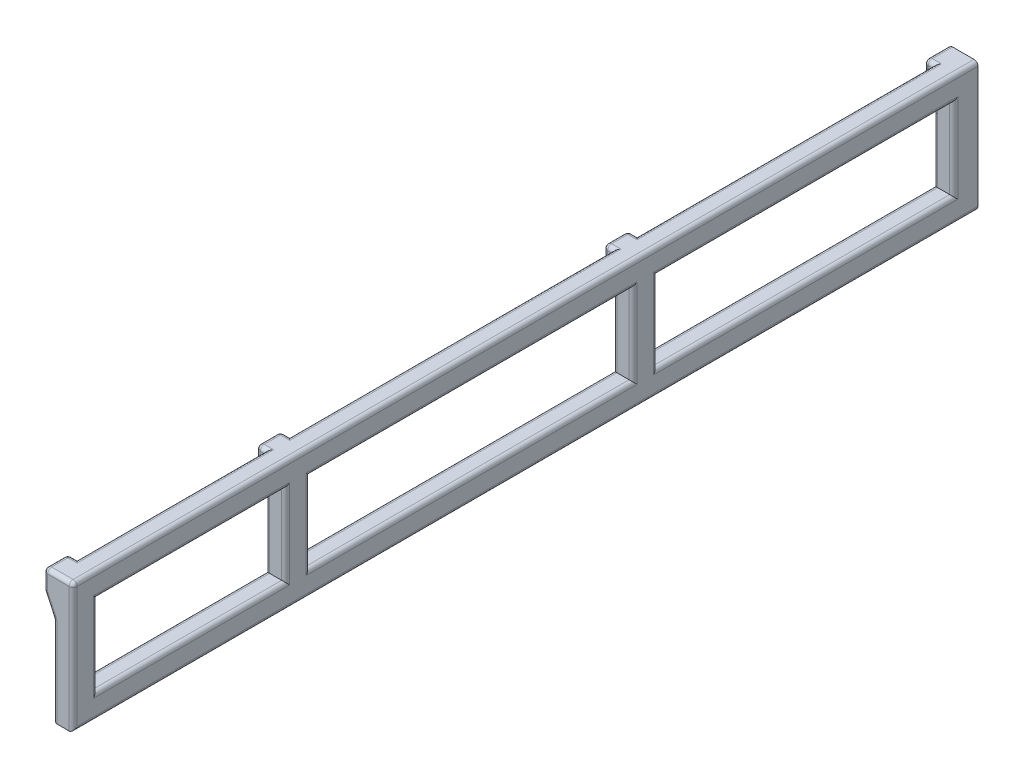
SolidWorks part; units mm, degrees
ref_plane "Plano frontal" through (0, 0, 0) normal (0, 0, 1) x (1, 0, 0)
ref_plane "Plano superior" through (0, 0, 0) normal (0, 1, 0) x (1, 0, 0)
ref_plane "Plano direito" through (0, 0, 0) normal (1, 0, 0) x (0, 0, -1)
sketch "Esboço8" plane through (0, 0, 0) normal (1, 0, 0) x (0, 0, -1)
  line L0 (-69.8214, 36) -> (10.1786, 36)
  line L1 (95.5586, 10) -> (-128.4414, 10)
  line L3 (89.5586, 16) -> (16.1786, 16)
  line L5 (-128.4414, 42) -> (70.1715, 42)
  line L7 (-122.4414, 36) -> (-75.8214, 36)
  line L8 (89.5586, 36) -> (89.5586, 16)
  line L10 (-75.8214, 36) -> (-75.8214, 16)
  line L12 (-69.8214, 36) -> (-69.8214, 16)
  line L14 (16.1786, 36) -> (16.1786, 16)
  line L16 (10.1786, 36) -> (10.1786, 16)
  line L17 (-75.8214, 16) -> (-122.4414, 16)
  line L18 (16.1786, 36) -> (89.5586, 36)
  line L19 (10.1786, 16) -> (-69.8214, 16)
  line L20 (-128.4414, 42) -> (-128.4414, 10)
  line L22 (-122.4414, 16) -> (-122.4414, 36)
  line L24 (70.1715, 42) -> (95.5586, 42)
  line L25 (95.5586, 42) -> (95.5586, 10)
  dimension "D2" = 224
  dimension "D3" = 80
  dimension "D4" = 52.62
  dimension "D5" = 6
  dimension "D6" = 20
  dimension "D8" = 6
  dimension "D9" = 6
  dimension "D10" = 6
extrude "Ressalto-extrusão1" add sketch "Esboço8" against normal blind 5
sketch "Esboço9" plane through (0, 0, 75.8214) normal (0, 0, 1) x (1, 0, 0)
  line L1 (-7.2996, 42) -> (-5, 42)
  line L4 (-5, 42) -> (-5, 32.1044)
  line L6 (-7.2996, 37.0359) -> (-5, 32.1044)
  line L7 (-7.2996, 42) -> (-7.2996, 37.0359)
extrude "Ressalto-extrusão2" add sketch "Esboço9" against normal blind 6
sketch "Esboço10" plane through (0, 0, -10.1786) normal (0, 0, 1) x (1, 0, 0)
  line L8 (0, 16) -> (0, 36)
  line L9 (0, 36) -> (-5, 36)
  line L10 (-5, 36) -> (-5, 42)
  line L11 (-5, 42) -> (-7.2996, 42)
  line L12 (-5, 42) -> (-7.2996, 42)
  line L13 (-7.2996, 42) -> (-7.2996, 37.0359)
  line L14 (-7.2996, 42) -> (-7.2996, 37.0359)
  line L15 (-5, 16) -> (0, 16)
  line L18 (-5, 32.1044) -> (-5, 42)
  line L22 (-7.2996, 37.0359) -> (-5, 32.1044)
  line L23 (-7.2996, 37.0359) -> (-5, 32.1044)
  line L24 (-5, 32.1044) -> (-5, 16)
  line M11 (-5, 36) -> (-5, 16)
  dimension "D1" = 0
extrude "Ressalto-extrusão3" add sketch "Esboço10" against normal blind 6 contours L14 L23 L18 L12 M11 region at (-6.0226, 38.1487, -10.1786)
sketch "Esboço11" plane through (0, 0, 128.4414) normal (0, 0, 1) x (1, 0, 0)
  line L8 (0, 16) -> (0, 36)
  line L9 (0, 36) -> (-5, 36)
  line L10 (-5, 36) -> (-5, 42)
  line L11 (-5, 42) -> (-7.2996, 42)
  line L12 (-5, 42) -> (-7.2996, 42)
  line L13 (-7.2996, 42) -> (-7.2996, 37.0359)
  line L14 (-7.2996, 42) -> (-7.2996, 37.0359)
  line L15 (-5, 16) -> (0, 16)
  line L18 (-5, 32.1044) -> (-5, 42)
  line L22 (-7.2996, 37.0359) -> (-5, 32.1044)
  line L23 (-7.2996, 37.0359) -> (-5, 32.1044)
  line L24 (-5, 32.1044) -> (-5, 16)
  line M11 (-5, 42) -> (-5, 10)
  dimension "D1" = 0
extrude "Ressalto-extrusão4" add sketch "Esboço11" against normal blind 6 contours L14 L23 L12 M11 region at (-6.0226, 38.1487, 128.4414)
sketch "Esboço12" plane through (0, 0, -89.5586) normal (0, 0, 1) x (1, 0, 0)
  line L6 (0, 10) -> (0, 42)
  line L7 (0, 42) -> (-7.2996, 42)
  line L8 (-7.2996, 42) -> (-7.2996, 37.0359)
  line L9 (-7.2996, 42) -> (-7.2996, 37.0359)
  line L10 (-5, 32.1044) -> (-5, 10)
  line L11 (-5, 10) -> (0, 10)
  line L13 (-5, 42) -> (-7.2996, 42)
  line L16 (-5, 42) -> (-5, 32.1044)
  line L17 (-7.2996, 37.0359) -> (-5, 32.1044)
  line L18 (-7.2996, 37.0359) -> (-5, 32.1044)
  dimension "D1" = 0
extrude "Ressalto-extrusão5" add sketch "Esboço12" against normal blind 6
fillet "Filete1" radius 1 65 edges at (-6.1498, 34.5701, 69.8214) (-6.1498, 34.5701, 75.8214) (-7.2996, 37.0359, 72.8214) (-7.2996, 39.5179, 69.8214) (-7.2996, 39.5179, 75.8214) (-7.2996, 37.0359, 125.4414) (-7.2996, 37.0359, -13.1786) (-3.6498, 42, 128.4414) (-7.2996, 42, 125.4414) (-6.1498, 42, 122.4414) (-5, 42, 99.1314) (-6.1498, 42, 75.8214) (-7.2996, 42, 72.8214) (-6.1498, 42, 69.8214) (-5, 42, 29.8214) (-6.1498, 42, -10.1786) (-7.2996, 42, -13.1786) (-6.1498, 42, -16.1786) (-5, 42, -52.8686) (-6.1498, 42, -89.5586) (0, 10, 16.4414) (0, 26, 128.4414) (0, 42, 16.4414) (0, 26, -16.1786) (0, 16, -52.8686) (0, 26, -89.5586) (0, 36, -52.8686) (0, 26, 75.8214) (0, 36, 99.1314) (0, 26, 122.4414) (0, 16, 99.1314) (0, 36, 29.8214) (0, 26, 69.8214) (0, 16, 29.8214) (0, 26, -10.1786) (-5, 24.0522, -89.5586) (-5, 16, -52.8686) (-5, 24.0522, -16.1786) (-5, 32.1044, -13.1786) (-5, 24.0522, -10.1786) (-5, 16, 29.8214) (-5, 24.0522, 69.8214) (-5, 32.1044, 72.8214) (-5, 24.0522, 75.8214) (-5, 16, 99.1314) (-5, 24.0522, 122.4414) (-5, 32.1044, 125.4414) (-5, 21.0522, 128.4414) (-5, 10, 16.4414) (-5, 36, -52.8686) (-5, 36, 29.8214) (-5, 36, 99.1314) (-6.1498, 34.5701, -89.5586) (-6.1498, 34.5701, 122.4414) (-6.1498, 34.5701, 128.4414) (-6.1498, 34.5701, -16.1786) (-6.1498, 34.5701, -10.1786) (-7.2996, 39.5179, 122.4414) (-7.2996, 39.5179, 128.4414) (-7.2996, 39.5179, -16.1786) (-7.2996, 39.5179, -10.1786) (-7.2996, 42, -92.5586) (-5, 32.1044, -92.5586) (-7.2996, 37.0359, -92.5586) (-7.2996, 39.5179, -89.5586)
fillet "Filete2" radius 1 4 edges at (-5.0237, 32.0991, -95.5586) (-7.2759, 37.0411, -95.5586) (-6.1498, 34.5701, -95.5586) (-7.2996, 39.1288, -95.5586) tangent propagation no
